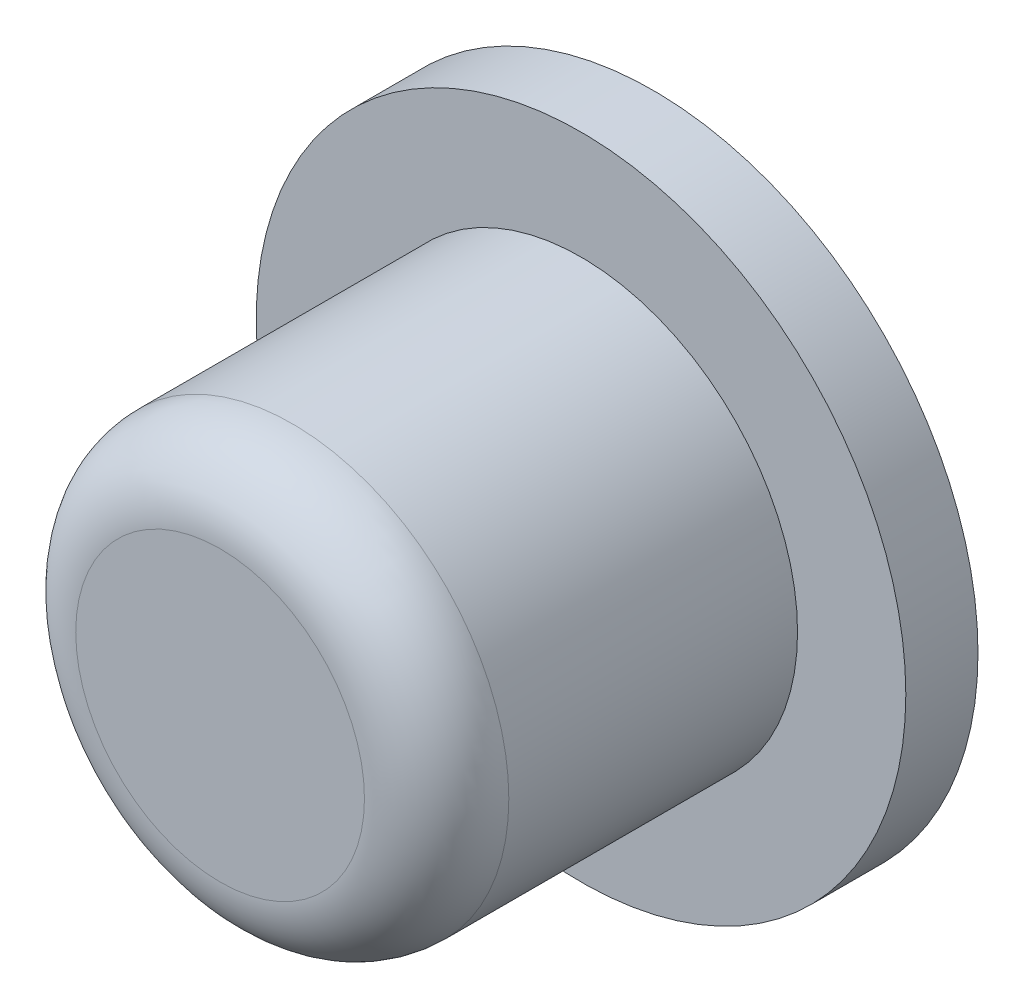
SolidWorks part; units mm, degrees
ref_plane "前视基准面" through (0, 0, 0) normal (0, 0, 1) x (1, 0, 0)
ref_plane "上视基准面" through (0, 0, 0) normal (0, 1, 0) x (1, 0, 0)
ref_plane "右视基准面" through (0, 0, 0) normal (1, 0, 0) x (0, 0, -1)
other "Configuration Table"
sketch "草图1" plane through (0, 0, 0) normal (0, 0, 1) x (1, 0, 0)
  circle A0 centre (0, 0) radius 1.9
  circle A1 centre (0, 0) radius 3
  circle A2 centre (0, 0) radius 4.5
  point P7 (0, 0)
  dimension "D4" = 3.8
  dimension "D1" = 6
  dimension "D2" = 1.5
extrude "凸台-拉伸1" add sketch "草图1" along normal blind 6 contours A1
extrude "切除-拉伸1" cut sketch "草图1<4>" along normal blind 2 contours A0
sketch "草图1<4>" plane through (0, 0, 0) normal (0, 0, 1) x (1, 0, 0) same geometry as "草图1"
extrude "凸台-拉伸2" add sketch "草图1<5>" along normal blind 1 contours A2 | A1
sketch "草图1<5>" plane through (0, 0, 0) normal (0, 0, 1) x (1, 0, 0) same geometry as "草图1"
fillet "圆角1" radius 1 1 edges at (3, 0, 6)
